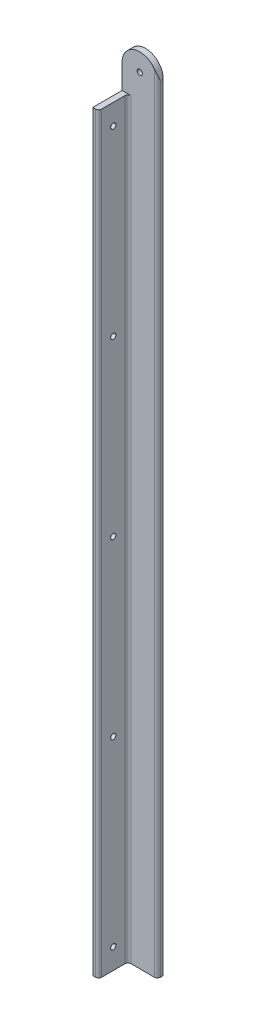
SolidWorks part; units mm, degrees
material "6061 Alloy"
ref_plane "Front Plane" through (0, 0, 0) normal (0, 0, 1) x (1, 0, 0)
ref_plane "Top Plane" through (0, 0, 0) normal (0, 1, 0) x (1, 0, 0)
ref_plane "Right Plane" through (0, 0, 0) normal (1, 0, 0) x (0, 0, -1)
sketch "Sketch2" plane through (0, 0, 0) normal (0, 1, 0) x (1, 0, 0)
  line L0 (0, 0) -> (19.05, 0)
  line L1 (0, 0) -> (0, 19.05)
  line L2 (4.7625, 3.175) -> (17.4625, 3.175)
  line L3 (3.175, 4.7625) -> (3.175, 17.4625)
  line L4 (0, 19.05) -> (1.5875, 19.05)
  line L5 (19.05, 1.5875) -> (19.05, 0)
  line L6 (3.175, 3.175) -> (3.175, 19.05) construction
  line L7 (3.175, 3.175) -> (19.05, 3.175) construction
  arc A0 (3.175, 17.4625) -> (1.5875, 19.05) centre (1.5875, 17.4625) ccw
  arc A1 (3.175, 4.7625) -> (4.7625, 3.175) centre (4.7625, 4.7625) ccw
  arc A2 (17.4625, 3.175) -> (19.05, 1.5875) centre (17.4625, 1.5875) cw
  dimension "D2" = 1.5875
  dimension "D1" = 3.175
extrude "Boss-Extrude1" add sketch "Sketch2" along normal blind 431.8
sketch "Sketch4" plane through (3.175, 0, 0) normal (1, 0, 0) x (0, 0, -1)
  line L0 (19.05, 431.8) -> (19.05, 406.4)
  line L1 (19.05, 431.8) -> (19.05, 0) construction
  line L2 (19.05, 406.4) -> (3.175, 406.4)
  line L3 (3.175, 431.8) -> (3.175, 0) construction
  line L4 (3.175, 406.4) -> (3.175, 431.8)
  line L5 (3.175, 431.8) -> (19.05, 431.8)
extrude "Cut-Extrude1" cut sketch "Sketch4" against normal blind 6.35
sketch "Sketch5" plane through (3.175, 0, 0) normal (-1, 0, 0) x (0, 0, 1)
  line L8 (-4.7625, 406.4) -> (-3.175, 406.4)
  line L9 (-3.175, 406.4) -> (-3.175, 431.8)
  line L10 (-3.175, 431.8) -> (-4.7625, 431.8)
  line L11 (-4.7625, 431.8) -> (-4.7625, 406.4)
  line L12 (-4.7625, 406.4) -> (-3.175, 406.4)
  line L13 (-3.175, 406.4) -> (-3.175, 431.8)
  line L14 (-3.175, 431.8) -> (-4.7625, 431.8)
  line L15 (-4.7625, 431.8) -> (-4.7625, 406.4)
  dimension "D1" = 0
extrude "Cut-Extrude2" cut sketch "Sketch5" against normal blind 6.35
sketch "Sketch6" plane through (3.175, 0, 0) normal (1, 0, 0) x (0, 0, -1)
  line L0 (19.05, 0) -> (3.175, 0) construction
  line L1 (11.1125, 0) -> (11.1125, 15.875) construction
  line L2 (19.05, 406.4) -> (3.175, 406.4) construction
  line L3 (11.1125, 406.4) -> (11.1125, 390.525) construction
  line L4 (11.1125, 15.875) -> (11.1125, 203.2) construction
  line L5 (11.1125, 203.2) -> (11.1125, 390.525) construction
  circle A1 centre (11.1125, 109.5375) radius 1.4224
  circle A2 centre (11.1125, 203.2) radius 1.4224
  circle A3 centre (11.1125, 296.8625) radius 1.4224
  circle A5 centre (11.1125, 11.1125) radius 1.4224
  circle A6 centre (11.1125, 395.2875) radius 1.4224
  point P12 (11.1125, 203.2)
  point P13 (11.1125, 296.8625)
  point P15 (11.1125, 109.5375)
  dimension "D2" = 2.8448
  dimension "D3" = 2.8448
  dimension "D4" = 2.8448
  dimension "D6" = 2.8448
  dimension "D7" = 2.8448
extrude "Cut-Extrude3" cut sketch "Sketch6" against normal blind 5.08
sketch "Sketch7" plane through (0, 431.8, 0) normal (0, 1, 0) x (1, 0, 0)
  line L8 (17.4625, 3.175) -> (0, 3.175)
  line L9 (0, 3.175) -> (0, 0)
  line L10 (0, 0) -> (19.05, 0)
  line L11 (19.05, 0) -> (19.05, 1.5875)
  line L12 (17.4625, 3.175) -> (0, 3.175)
  line L13 (0, 3.175) -> (0, 0)
  line L14 (0, 0) -> (19.05, 0)
  line L15 (19.05, 0) -> (19.05, 1.5875)
  arc A2 (19.05, 1.5875) -> (17.4625, 3.175) centre (17.4625, 1.5875) ccw
  arc A3 (19.05, 1.5875) -> (17.4625, 3.175) centre (17.4625, 1.5875) ccw
  dimension "D1" = 0
extrude "Cut-Extrude4" cut sketch "Sketch7" against normal blind 2.54
sketch "Sketch8" plane through (0, 0, -3.175) normal (0, 0, -1) x (-1, 0, 0)
  line L0 (0, 429.26) -> (0, 419.735) construction
  line L1 (0, 429.26) -> (0, 406.4) construction
  line L2 (0, 419.735) -> (-9.525, 419.735) construction
  circle A0 centre (-9.525, 419.735) radius 1.4224
  dimension "D1" = 2.8448
extrude "Cut-Extrude5" cut sketch "Sketch8" against normal blind 5.08
ref_plane "Plane1" through (0, 0, 2.54) normal (0, 0, 1) x (1, 0, 0)
mirror "Mirror3" about plane through (0, 0, 2.54) normal (0, 0, 1) of bodies 106
sketch "Sketch9" plane through (0, 0, 2.54) normal (0, 0, 1) x (1, 0, 0)
  line L1 (-6.6248, 469.5409) -> (22.2362, 469.5409)
  line L2 (-6.6248, 469.5409) -> (-6.6248, -77.9837)
  line L3 (-6.6248, -77.9837) -> (22.2362, -77.9837)
  line L4 (22.2362, 469.5409) -> (22.2362, -77.9837)
extrude "Cut-Extrude6" cut sketch "Sketch9" against normal blind 30.48
sketch "Sketch10" plane through (0, 0, 8.255) normal (0, 0, 1) x (1, 0, 0)
  line L0 (9.525, 419.735) -> (9.525, 415.925) construction
  line L7 (19.05, 419.735) -> (19.05, 429.26)
  line L8 (19.05, 429.26) -> (0, 429.26)
  line L9 (0, 419.735) -> (0, 429.26)
  line L11 (19.05, 429.26) -> (9.525, 419.735) construction
  line L12 (9.525, 419.735) -> (0, 429.26) construction
  arc A3 (19.05, 419.735) -> (0, 419.735) centre (9.525, 419.735) ccw
  line M4 (17.4625, 429.26) -> (0, 429.26)
  line M5 (0, 429.26) -> (0, 406.4)
  line M9 (17.4625, 0) -> (17.4625, 429.26)
extrude "Cut-Extrude7" cut sketch "Sketch10" against normal blind 5.08 contours M9 | M9 M4 | M5 region at (18.3487, 426.1569, 8.255) region at (2.1276, 427.1324, 8.255) region at (15.5776, 428.0522, 8.255)
